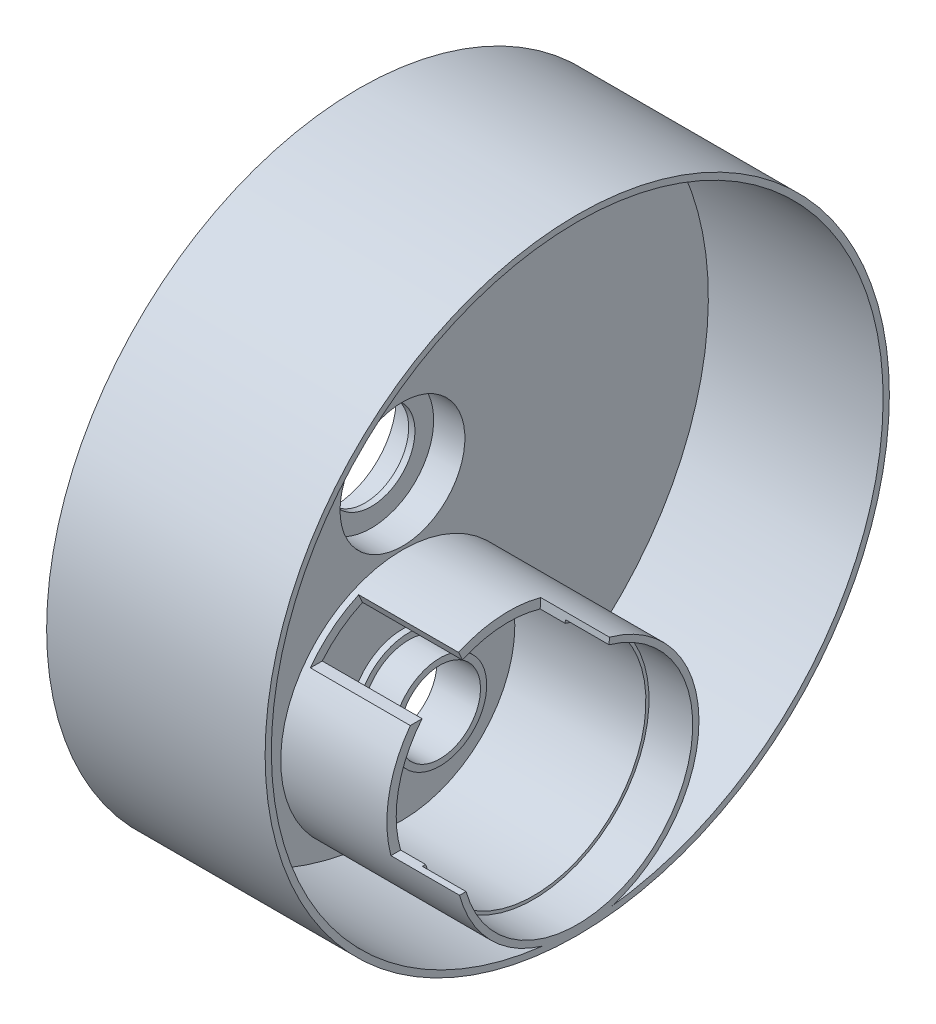
SolidWorks part; units mm, degrees
material "1060 Сплав"
ref_plane "Спереди" through (0, 0, 0) normal (0, 0, 1) x (1, 0, 0)
ref_plane "Сверху" through (0, 0, 0) normal (0, 1, 0) x (1, 0, 0)
ref_plane "Справа" through (0, 0, 0) normal (1, 0, 0) x (0, 0, -1)
sketch "Эскиз1" plane through (0, 0, 0) normal (0, 0, 1) x (1, 0, 0)
  line L0 (0, 0) -> (26039.5549, 0) construction
  line L1 (-27, 7.5) -> (-27, 8.5)
  line L2 (0, 19.5) -> (-29, 19.5)
  line L3 (-29, 19.5) -> (-29, 6.5)
  line L4 (-29, 6.5) -> (-22, 6.5)
  line L5 (-22, 6.5) -> (-22, 7.5)
  line L6 (-22, 7.5) -> (-27, 7.5)
  line L7 (-28, 8.5) -> (-28, 18)
  line L8 (-28, 18) -> (-7, 18)
  line L9 (-7, 18) -> (-7, 18.5)
  line L10 (-7, 18.5) -> (0, 18.5)
  line L11 (0, 18.5) -> (0, 19.5)
  line L12 (-27, 8.5) -> (-28, 8.5)
  dimension "D1" = 18.5
  dimension "D2" = 1
  dimension "D3" = 18
  dimension "D4" = 7
  dimension "D5" = 21
  dimension "D6" = 1
  dimension "D7" = 1
  dimension "D8" = 1
  dimension "D9" = 7.5
  dimension "D10" = 1
  dimension "D11" = 13
  dimension "D12" = 0.5
  dimension "D13" = 5
revolve "Повернуть1" add sketch "Эскиз1" angle 360 about L0
sketch "Эскиз2" plane through (0, 0, 0) normal (1, 0, 0) x (0, 0, -1)
  line L0 (0, 0) -> (0, 50000) construction
  line L1 (5.1563, 18.8059) -> (5, 16.2481)
  line L2 (5, 0) -> (5, 50000) construction
  line L3 (0, 0) -> (0, -5) construction
  line L4 (0, -5) -> (-50000, -5) construction
  line L5 (-18.8481, -5) -> (-16.2481, -5)
  line L6 (-5, 0) -> (-5, 50000) construction
  arc A0 (5, 16.2481) -> (-16.2481, -5) centre (0, 0) ccw
  arc A1 (-18.8481, -5) -> (5.1563, 18.8059) centre (0, 0) cw
  circle A2 centre (0, 0) radius 19.5 construction
  dimension "D3" = 17
  dimension "D4" = 19.5
  dimension "D1" = 5
  dimension "D2" = 5
  dimension "D5" = 2.5626
  dimension "D6" = 0
extrude "Вырез-Вытянуть1" cut sketch "Эскиз2" against normal blind 11 contours A0 L5 A1 L1
sketch "Эскиз3" plane through (0, 0, 0) normal (1, 0, 0) x (0, 0, -1)
  line L3 (-40, 11.5) -> (-12.52, 11.5)
  line L4 (0, 0) -> (-20535.6471, 45588.2353) construction
  line L5 (-6.9821, 15.5) -> (-13.2408, 29.394)
  line L6 (-13.2408, 29.394) -> (-40, 11.5)
  line L7 (0, 15.5) -> (-50000, 15.5) construction
  circle A0 centre (0, 0) radius 15.5 construction
  circle A1 centre (0, 0) radius 11.5 construction
  arc A2 (-6.9821, 15.5) -> (-12.52, 11.5) centre (0, 0) ccw
  dimension "D1" = 31
  dimension "D2" = 23
  dimension "D4" = 34
  dimension "D3" = 15.2386
  dimension "D5" = 32.1908
extrude "Вырез-Вытянуть2" cut sketch "Эскиз3" against normal blind 27
sketch "Эскиз4" plane through (-29, 0, 0) normal (-1, 0, 0) x (0, 0, 1)
  circle A1 centre (0, 30) radius 50
  circle A2 centre (0, 30) radius 10
  circle A3 centre (0, 0) radius 6.5 construction
  circle A4 centre (0, 0) radius 6.5
  dimension "D2" = 100
  dimension "D3" = 20
  dimension "D5" = 13
  dimension "D1" = 30
  dimension "D4" = 30
extrude "Бобышка-Вытянуть1" add sketch "Эскиз4" against normal blind 1
sketch "Эскиз5" plane through (-29, 0, 0) normal (-1, 0, 0) x (0, 0, 1)
  circle A0 centre (0, 30) radius 50
  circle A1 centre (0, 30) radius 49
  dimension "D1" = 100
  dimension "D2" = 98
extrude "Бобышка-Вытянуть2" add sketch "Эскиз5" against normal blind 29 and the other way blind 6
sketch "Эскиз9" plane through (0, 0, 0) normal (0, 0, 1) x (1, 0, 0)
  line L0 (-50.3474, 30) -> (12.875, 30) construction
  line L1 (-39, 40) -> (-34, 40)
  line L2 (-39, 41) -> (-29, 41)
  line L3 (-34, 40) -> (-34, 37)
  line L4 (-34, 37) -> (-33, 37)
  line L5 (-33, 37) -> (-33, 40)
  line L6 (-33, 40) -> (-29, 40)
  line L7 (-29, 40) -> (-29, 41)
  line L8 (-39, 41) -> (-39, 40)
  line L11 (-28, 20) -> (-28, 40) construction
  point P12 (0, 0)
  dimension "D1" = 30
  dimension "D2" = 1
  dimension "D3" = 5
  dimension "D4" = 5
  dimension "D5" = 11
  dimension "D6" = 3
revolve "Повернуть2" add sketch "Эскиз9" angle 360 about L0
